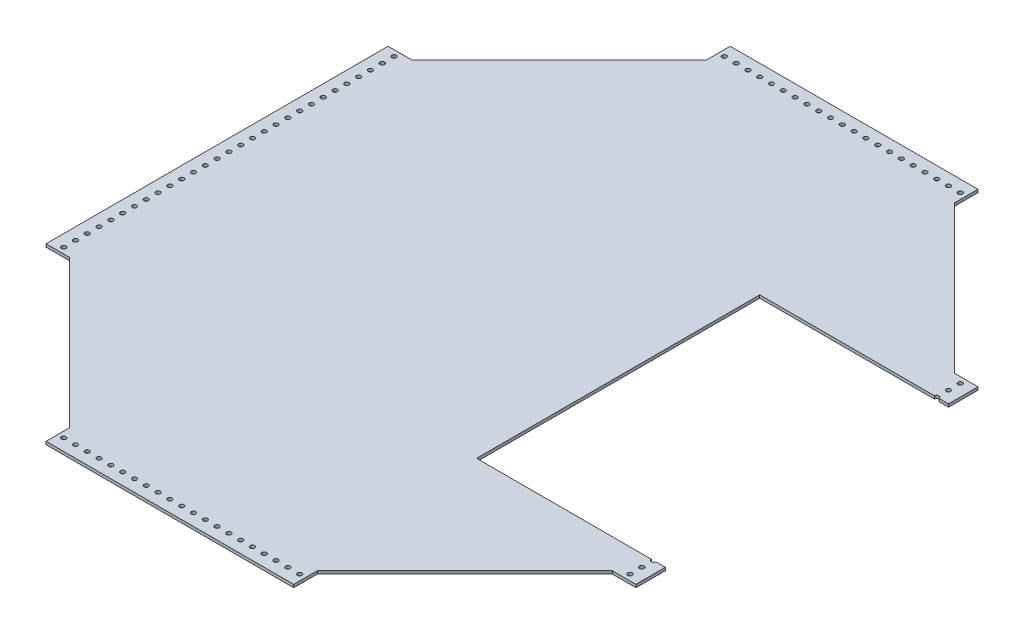
SolidWorks part; units mm, degrees
material "ABS PC"
ref_plane "Front Plane" through (0, 0, 0) normal (0, 0, 1) x (1, 0, 0)
ref_plane "Top Plane" through (0, 0, 0) normal (0, 1, 0) x (1, 0, 0)
ref_plane "Right Plane" through (0, 0, 0) normal (1, 0, 0) x (0, 0, -1)
sketch "Sketch1" plane through (0, 0, 0) normal (0, 1, 0) x (1, 0, 0)
  line L1 (-317.5, -368.3) -> (317.5, -368.3)
  line L2 (-317.5, -368.3) -> (-317.5, 368.3)
  line L3 (-317.5, 368.3) -> (317.5, 368.3)
  line L4 (317.5, -368.3) -> (317.5, 368.3)
  line L5 (-317.5, -368.3) -> (317.5, 368.3) construction
  line L6 (-317.5, 368.3) -> (317.5, -368.3) construction
  point P0 (0, 0)
  dimension "D1" = 635
  dimension "D2" = 736.6
extrude "Base" add sketch "Sketch1" along normal blind 3.175
sketch "Sketch3" plane through (0, 3.175, 0) normal (0, 1, 0) x (1, 0, 0)
  line L0 (317.5, -368.3) -> (317.5, 368.3) construction
  line L6 (317.5, 368.3) -> (-317.5, 368.3) construction
  line L7 (-317.5, 368.3) -> (-317.5, -368.3) construction
  circle A0 centre (-304.8, 355.6) radius 2.413
  circle A1 centre (304.8, 355.6) radius 2.413
  dimension "D1" = 4.826
  dimension "D2" = 4.826
  dimension "D3" = 12.7
  dimension "D4" = 12.7
  dimension "D5" = 12.7
  dimension "D6" = 12.7
extrude "Initial Pattern Hole" cut sketch "Sketch3" against normal through all
pattern_linear "Hole Pattern 1" count 58 spacing 12.7 along (0, 0, 1) of "Initial Pattern Hole"
pattern_linear "Hole Pattern 2" count 48 spacing 12.7 along (1, 0, 0) of face at (-304.8, 0, 358.013) of face at (-304.8, 0, -353.187)
sketch "Sketch2" plane through (0, 0, 0) normal (0, -1, 0) x (-1, 0, 0)
  line L16 (-317.5, 368.3) -> (-317.5, 184.15)
  line L17 (-317.5, -368.3) -> (-317.5, 368.3) construction
  line L18 (-317.5, 184.15) -> (-292.1004, 184.15)
  line L19 (-292.1004, 184.15) -> (-133.35, 342.9004)
  line L20 (-133.35, 342.9004) -> (-133.35, 368.3)
  line L21 (-317.5, 368.3) -> (317.5, 368.3) construction
  line L22 (-133.35, 368.3) -> (-317.5, 368.3)
  line L23 (133.35, 368.3) -> (317.5, 368.3)
  line L24 (317.5, 368.3) -> (317.5, 184.15)
  line L25 (317.5, 368.3) -> (317.5, -368.3) construction
  line L26 (317.5, 184.15) -> (292.1004, 184.15)
  line L27 (292.1004, 184.15) -> (133.35, 342.9004)
  line L28 (133.35, 342.9004) -> (133.35, 368.3)
  line L29 (317.5, -368.3) -> (317.5, -184.15)
  line L30 (317.5, -184.15) -> (292.1004, -184.15)
  line L31 (292.1004, -184.15) -> (133.35, -342.9004)
  line L32 (133.35, -342.9004) -> (133.35, -368.3)
  line L33 (317.5, -368.3) -> (307.213, -368.3) construction
  line L34 (133.35, -368.3) -> (317.5, -368.3)
  line L35 (-133.35, -368.3) -> (-133.35, -342.9004)
  line L36 (-133.35, -342.9004) -> (-292.1004, -184.15)
  line L37 (-292.1004, -184.15) -> (-317.5, -184.15)
  line L38 (-317.5, -184.15) -> (-317.5, -368.3)
  line L39 (-317.5, -368.3) -> (-133.35, -368.3)
  dimension "D1" = 184.15
extrude "Module Cutout" cut sketch "Sketch2" against normal through all
sketch "Sketch4" [suppressed] plane through (0, 3.175, 0) normal (0, 1, 0) x (1, 0, 0)
  line L24 (-317.5, 165.1) -> (-241.3, 165.1)
  line L25 (-317.5, 368.3) -> (-317.5, -368.3) construction
  line L26 (-241.3, 165.1) -> (-114.3, 292.1)
  line L27 (-114.3, 292.1) -> (-114.3, 368.3)
  line L28 (317.5, 368.3) -> (-317.5, 368.3) construction
  line L29 (-317.5, -368.3) -> (-114.3, -368.3)
  line L30 (-114.3, -368.3) -> (-114.3, -292.1)
  line L31 (-114.3, -292.1) -> (-241.3, -165.1)
  line L32 (-241.3, -165.1) -> (-317.5, -165.1)
  line L33 (-317.5, -165.1) -> (-317.5, -368.3)
  line L34 (-317.5, 165.1) -> (-317.5, 368.3)
  line L35 (-317.5, 368.3) -> (-114.3, 368.3)
  line L36 (317.5, 368.3) -> (114.3, 368.3)
  line L37 (114.3, 368.3) -> (114.3, 177.8)
  line L38 (114.3, 177.8) -> (317.5, 177.8)
  line L39 (317.5, 152.4) -> (317.5, 260.35) construction
  line L40 (317.5, 177.8) -> (317.5, 368.3)
  line L41 (317.5, -177.8) -> (114.3, -177.8)
  line L42 (317.5, -260.35) -> (317.5, -152.4) construction
  line L43 (114.3, -177.8) -> (114.3, -368.3)
  line L44 (-302.387, -368.3) -> (302.387, -368.3) construction
  line L45 (114.3, -368.3) -> (317.5, -368.3)
  line L46 (317.5, -368.3) -> (317.5, -177.8)
  dimension "D1" = 76.2
  dimension "D2" = 76.2
  dimension "D3" = 203.2
  dimension "D4" = 203.2
  dimension "D5" = 190.5
  dimension "D6" = 203.2
extrude "Top Module Cutout" [suppressed] cut sketch "Sketch4" against normal through all
sketch "Sketch5" plane through (0, 3.175, 0) normal (0, 1, 0) x (1, 0, 0)
  line L0 (317.5, 152.4) -> (114.3, 152.4)
  line L1 (114.3, 152.4) -> (114.3, -152.4)
  line L2 (114.3, -152.4) -> (317.5, -152.4)
  line L3 (317.5, -152.4) -> (317.5, 152.4)
extrude "Intake Cutout" cut sketch "Sketch5" against normal through all contours L2 L0 L1 | L2 L3 L0 region at (215.9, 3.175, 0)
